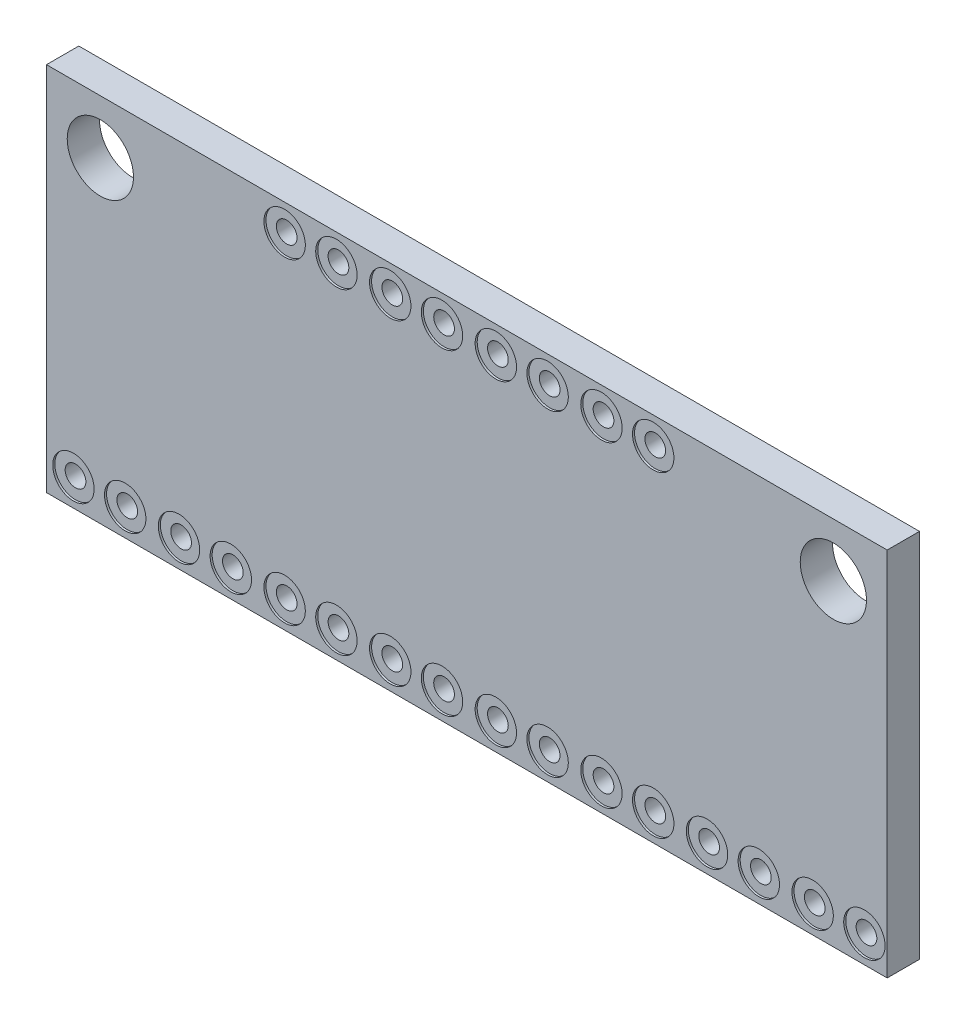
SolidWorks part; units mm, degrees
ref_plane "Alzado" through (0, 0, 0) normal (0, 0, 1) x (1, 0, 0)
ref_plane "Planta" through (0, 0, 0) normal (0, 1, 0) x (1, 0, 0)
ref_plane "Vista lateral" through (0, 0, 0) normal (1, 0, 0) x (0, 0, -1)
sketch "Croquis1" plane through (0, 0, 0) normal (0, 0, 1) x (1, 0, 0)
  line L0 (-20.3, 8.95) -> (-17.7, 8.95) construction
  line L1 (-20.3, 8.95) -> (20.3, 8.95)
  line L2 (-20.3, 8.95) -> (-20.3, -8.95)
  line L3 (-20.3, -8.95) -> (20.3, -8.95)
  line L4 (20.3, 8.95) -> (20.3, -8.95)
  line L5 (-20.3, 8.95) -> (20.3, -8.95) construction
  line L6 (-20.3, -8.95) -> (20.3, 8.95) construction
  line L7 (-17.7, 8.95) -> (-17.7, 6.35) construction
  line L8 (0, 8.95) -> (0, 15.6897) construction
  circle A0 centre (-17.7, 6.35) radius 1.6
  circle A1 centre (17.7, 6.35) radius 1.6
  point P0 (0, 0)
  dimension "D5" = 3.2
  dimension "D1" = 40.6
  dimension "D2" = 17.9
  dimension "D3" = 2.6
  dimension "D4" = 2.6
extrude "Saliente-Extruir1" add sketch "Croquis1" along normal blind 1.56
sketch "Croquis2" plane through (0, 0, 1.56) normal (0, 0, 1) x (1, 0, 0)
  line L0 (-20.3, -8.95) -> (-19, -8.95) construction
  line L1 (-20.3, -8.95) -> (20.3, -8.95) construction
  line L2 (-19, -8.95) -> (-19, -7.65) construction
  line L3 (-18.5, -7.65) -> (-16.5, -7.65) construction
  line L4 (-20.3, 0) -> (-24.4947, 0) construction
  line L5 (-20.3, 8.95) -> (-20.3, -8.95) construction
  circle A0 centre (-19, -7.65) radius 0.5
  circle A1 centre (-16.5, -7.65) radius 0.5
  circle A2 centre (-13.9, -7.65) radius 0.5
  circle A3 centre (-11.4, -7.65) radius 0.5
  circle A4 centre (-8.8, -7.65) radius 0.5
  circle A5 centre (-6.3, -7.65) radius 0.5
  circle A6 centre (-3.7, -7.65) radius 0.5
  circle A7 centre (-1.2, -7.65) radius 0.5
  circle A8 centre (1.4, -7.65) radius 0.5
  circle A9 centre (3.9, -7.65) radius 0.5
  circle A10 centre (6.5, -7.65) radius 0.5
  circle A11 centre (9, -7.65) radius 0.5
  circle A12 centre (11.6, -7.65) radius 0.5
  circle A13 centre (14.1, -7.65) radius 0.5
  circle A14 centre (16.7, -7.65) radius 0.5
  circle A15 centre (19.2, -7.65) radius 0.5
  circle A16 centre (9, 7.65) radius 0.5
  circle A17 centre (6.5, 7.65) radius 0.5
  circle A18 centre (3.9, 7.65) radius 0.5
  circle A19 centre (1.4, 7.65) radius 0.5
  circle A20 centre (-1.2, 7.65) radius 0.5
  circle A21 centre (-3.7, 7.65) radius 0.5
  circle A22 centre (-6.3, 7.65) radius 0.5
  circle A23 centre (-8.8, 7.65) radius 0.5
  dimension "D3" = 1
  dimension "D5" = 1
  dimension "D1" = 1.3
  dimension "D2" = 1.3
  dimension "D4" = 2
  dimension "D6" = 8
extrude "Cortar-Extruir1" cut sketch "Croquis2" against normal through all
sketch "Croquis3" plane through (0, 0, 1.56) normal (0, 0, 1) x (1, 0, 0)
  line L0 (-20.3, 0) -> (-24.2174, 0) construction
  line L1 (-20.3, 8.95) -> (-20.3, -8.95) construction
  circle A0 centre (-19, -7.65) radius 0.5
  circle A1 centre (-19, -7.65) radius 1
  circle A2 centre (-16.5, -7.65) radius 1
  circle A4 centre (-11.4, -7.65) radius 1
  circle A5 centre (-13.9, -7.65) radius 1
  circle A6 centre (-6.3, -7.65) radius 1
  circle A7 centre (-8.8, -7.65) radius 1
  circle A8 centre (-1.2, -7.65) radius 1
  circle A9 centre (-3.7, -7.65) radius 1
  circle A10 centre (3.9, -7.65) radius 1
  circle A11 centre (1.4, -7.65) radius 1
  circle A12 centre (9, -7.65) radius 1
  circle A13 centre (6.5, -7.65) radius 1
  circle A14 centre (14.1, -7.65) radius 1
  circle A15 centre (11.6, -7.65) radius 1
  circle A16 centre (19.2, -7.65) radius 1
  circle A17 centre (16.7, -7.65) radius 1
  circle A18 centre (9, 7.65) radius 1
  circle A19 centre (6.5, 7.65) radius 1
  circle A20 centre (3.9, 7.65) radius 1
  circle A21 centre (1.4, 7.65) radius 1
  circle A22 centre (-1.2, 7.65) radius 1
  circle A23 centre (-3.7, 7.65) radius 1
  circle A24 centre (-6.3, 7.65) radius 1
  circle A25 centre (-8.8, 7.65) radius 1
  dimension "D1" = 2
  dimension "D2" = 2
  dimension "D3" = 8
extrude "Cortar-Extruir2" cut sketch "Croquis3" against normal blind 0.1 contours A1 | A2 | A5 | A4 | A7 | A6 | A9 | A8 | A11 | A10 | A13 | A12 | A15 | A14 | A17 | A16 | A18 | A19 | A20 | A21 | A22 | A23 | A24 | A25
sketch "Croquis6" plane through (0, 0, 0) normal (0, 0, 1) x (1, 0, 0)
  text T0 "C15" font "Futura Md BT" height 0.7
  text T1 "C14" font "Futura Md BT" height 0.7
  text T2 "C13" font "Futura Md BT" height 0.7
  text T3 "C12" font "Futura Md BT" height 0.7
  text T4 "C11" font "Futura Md BT" height 0.7
  text T5 "C10" font "Futura Md BT" height 0.7
  text T6 "C09" font "Futura Md BT" height 0.7
  text T7 "C08" font "Futura Md BT" height 0.7
  text T8 "C07" font "Futura Md BT" height 0.7
  text T9 "C06" font "Futura Md BT" height 0.7
  text T10 "C05" font "Futura Md BT" height 0.7
  text T11 "C04" font "Futura Md BT" height 0.7
  text T12 "C03" font "Futura Md BT" height 0.7
  text T13 "C02" font "Futura Md BT" height 0.7
  text T14 "C01" font "Futura Md BT" height 0.7
  text T15 "C00" font "Futura Md BT" height 0.7
  text T16 "SIG" font "Futura Md BT" height 0.7
  text T17 "S3" font "Futura Md BT" height 0.7
  text T18 "S2" font "Futura Md BT" height 0.7
  text T19 "S1" font "Futura Md BT" height 0.7
  text T20 "S0" font "Futura Md BT" height 0.7
  text T21 "EN" font "Futura Md BT" height 0.7
  text T22 "VCC" font "Futura Md BT" height 0.7
  text T23 "GND" font "Futura Md BT" height 0.7
  point P3 (0, 0)
  point P4 (0, 0)
  point P21 (0, 0)
  point P30 (0, 0)
  point P32 (0, 0)
  point P33 (0, 0)
  point P34 (0, 0)
  point P35 (0, 0)
  point P36 (0, 0)
  point P37 (0, 0)
  point P38 (0, 0)
  point P39 (0, 0)
  point P40 (0, 0)
  point P41 (0, 0)
  point P42 (0, 0)
  point P43 (0, 0)
extrude "Cortar-Extruir4" cut sketch "Croquis6" along normal blind 0.1
